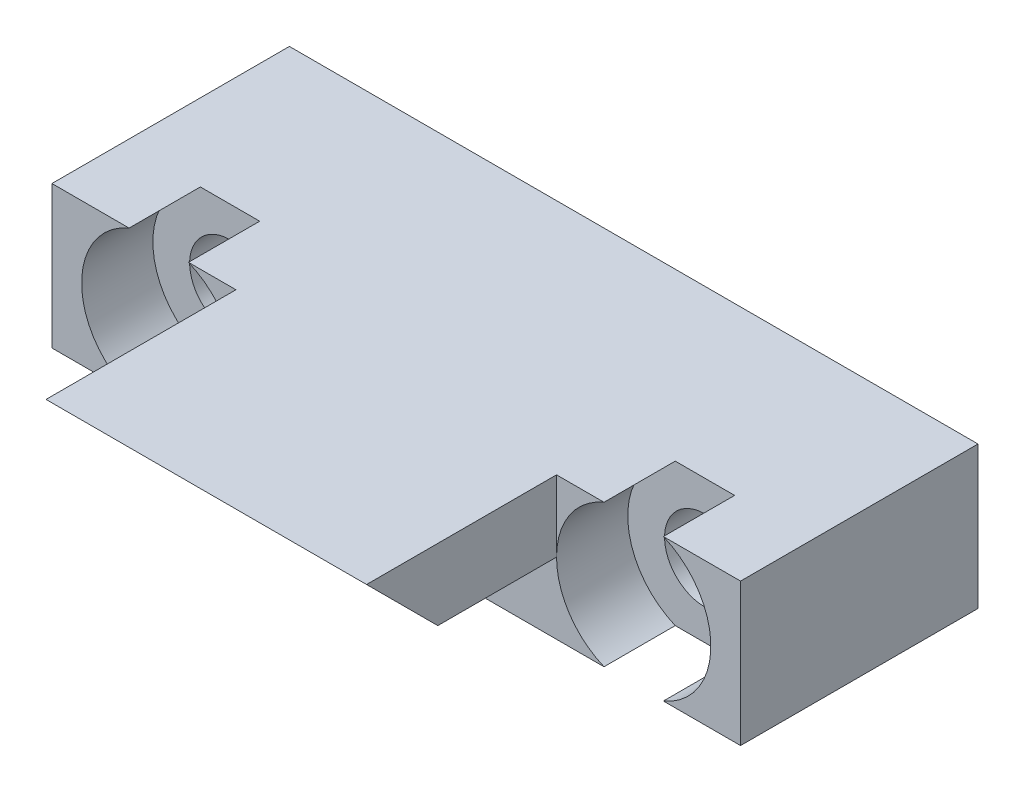
SolidWorks part; units mm, degrees
ref_plane "Front Plane" through (0, 0, 0) normal (0, 0, 1) x (1, 0, 0)
ref_plane "Top Plane" through (0, 0, 0) normal (0, 1, 0) x (1, 0, 0)
ref_plane "Right Plane" through (0, 0, 0) normal (1, 0, 0) x (0, 0, -1)
sketch "Sketch1" plane through (0, 0, 0) normal (0, 0, 1) x (1, 0, 0)
  line L1 (-14.5, -3) -> (14.5, -3)
  line L2 (-14.5, -3) -> (-14.5, 3)
  line L3 (-14.5, 3) -> (14.5, 3)
  line L4 (14.5, -3) -> (14.5, 3)
  line L5 (-14.5, -3) -> (14.5, 3) construction
  line L6 (-14.5, 3) -> (14.5, -3) construction
  point P0 (0, 0)
  dimension "D1" = 6
  dimension "D2" = 29
extrude "Boss-Extrude1" add sketch "Sketch1" along normal blind 10
sketch "Sketch5" plane through (0, 0, 10) normal (0, 0, 1) x (1, 0, 0)
  line L1 (-6.75, 3) -> (6.75, 3)
  line L2 (-6.75, 3) -> (-6.75, 0)
  line L3 (-6.75, 0) -> (6.75, 0)
  line L4 (6.75, 3) -> (6.75, 0)
  line L6 (14.5, 3) -> (-14.5, 3) construction
  point P5 (0, 0)
  dimension "D1" = 3
  dimension "D2" = 13.5
extrude "Boss-Extrude2" add sketch "Sketch5" along normal blind 8
hole_wizard "CBORE for M3 SHCS1" positions "Sketch2" profile "Sketch4" counterbore size "M3" standard "ANSI Metric" end condition through all
sketch "Sketch2" plane through (0, 0, 10) normal (0, 0, 1) x (1, 0, 0)
  line L0 (-10, 0) -> (10, 0)
  point P1 (-10, 0)
  point P2 (10, 0)
  point P4 (0, 0)
  dimension "D1" = 20
sketch "Sketch4" plane through (-10, 0, 10) normal (1, 0, 0) x (0, -1, 0)
  line L0 (0, 0) -> (0, 10)
  line L1 (0, 10) -> (1.7, 10)
  line L3 (1.7, 10) -> (1.7, 3)
  line L4 (1.7, 3) -> (3.25, 3)
  line L5 (3.25, 3) -> (3.25, 0)
  line L7 (3.25, 0) -> (0, 0)
  line L11 (0, -6.35) -> (0, 107.95) construction
  dimension "Thru Hole Dia." = 3.4
  dimension "Thru Hole Depth" = 10
  dimension "C'Bore Dia." = 6.5
  dimension "C'Bore Depth" = 3
chamfer "Chamfer1" distance 3 angle 45 1 edges at (0, 0, 18)
